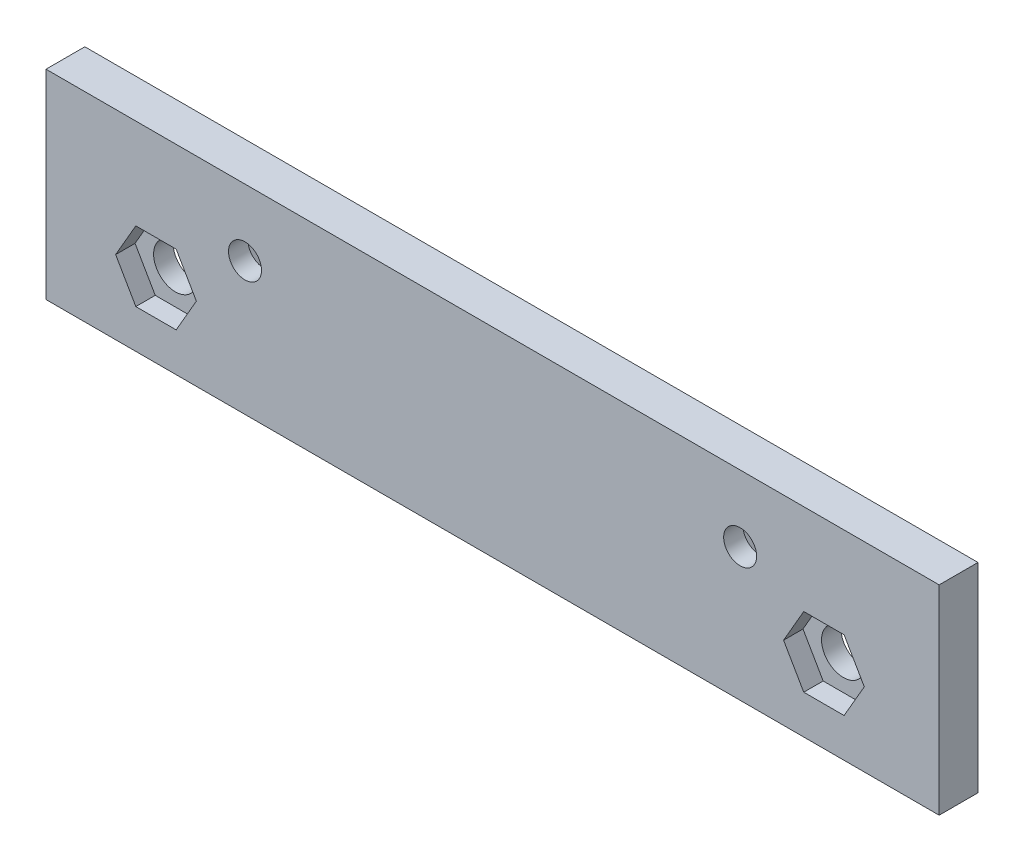
SolidWorks part; units mm, degrees
ref_plane "Front Plane" through (0, 0, 0) normal (0, 0, 1) x (1, 0, 0)
ref_plane "Top Plane" through (0, 0, 0) normal (0, 1, 0) x (1, 0, 0)
ref_plane "Right Plane" through (0, 0, 0) normal (1, 0, 0) x (0, 0, -1)
sketch "Sketch1" plane through (0, 0, 0) normal (0, 0, 1) x (1, 0, 0)
  line L1 (46, -37.5) -> (-46, -37.5)
  line L2 (46, -37.5) -> (46, 37.5)
  line L3 (46, 37.5) -> (-46, 37.5)
  line L4 (-46, -37.5) -> (-46, 37.5)
  line L5 (46, -37.5) -> (-46, 37.5) construction
  line L6 (46, 37.5) -> (-46, -37.5) construction
  point P0 (0, 0)
  dimension "D1" = 92
  dimension "D2" = 75
extrude "Boss-Extrude1" add sketch "Sketch1" along normal blind 4
sketch "Sketch2" plane through (0, 0, 4) normal (0, 0, 1) x (1, 0, 0)
  line L0 (-34.6699, -1.6) -> (34.1301, -1.6) construction
  line L1 (46, 37.5) -> (-46, 37.5) construction
  point P6 (0, 0)
  dimension "D1" = 39.1
  dimension "D2" = 34.1301
  dimension "D3" = 68.8
hole_wizard "M4 Clearance Hole1" positions "Sketch3" profile "Sketch4" hole size "M4" standard "DIN" end condition through all
sketch "Sketch3" plane through (0, 0, 4) normal (0, 0, 1) x (1, 0, 0)
  point P0 (-34.6699, -1.6)
  point P3 (34.1301, -1.6)
sketch "Sketch4" plane through (-34.6699, -1.6, 4) normal (1, 0, 0) x (0, -1, 0)
  line L0 (0, 0) -> (0, 4)
  line L1 (0, 4) -> (2.25, 4)
  line L2 (2.25, 4) -> (2.25, 0)
  line L5 (2.25, 0) -> (0, 0)
  line L11 (0, -6.35) -> (0, 107.95) construction
  dimension "Thru Hole Dia." = 4.5
  dimension "Thru Hole Depth" = 4
sketch "Sketch5" plane through (0, 0, 4) normal (0, 0, 1) x (1, 0, 0)
  line L0 (-25.5, 4.5) -> (25.5, 4.5)
  line L1 (-46, -37.5) -> (46, -37.5) construction
  dimension "D1" = 51
  dimension "D2" = 25.5
  dimension "D3" = 42
hole_wizard "M3 Clearance Hole1" positions "Sketch6" profile "Sketch7" hole size "M3" standard "DIN" end condition through all
sketch "Sketch6" plane through (0, 0, 4) normal (0, 0, 1) x (1, 0, 0)
  point P0 (-25.5, 4.5)
  point P3 (25.5, 4.5)
sketch "Sketch7" plane through (-25.5, 4.5, 4) normal (1, 0, 0) x (0, -1, 0)
  line L0 (0, 0) -> (0, 4)
  line L1 (0, 4) -> (1.7, 4)
  line L2 (1.7, 4) -> (1.7, 0)
  line L5 (1.7, 0) -> (0, 0)
  line L11 (0, -6.35) -> (0, 107.95) construction
  dimension "Thru Hole Dia." = 3.4
  dimension "Thru Hole Depth" = 4
sketch "Sketch8" plane through (0, 0, 4) normal (0, 0, 1) x (1, 0, 0)
  line L1 (-30.513, -1.6) -> (-32.5914, 2)
  line L2 (-32.5914, 2) -> (-36.7483, 2)
  line L3 (-36.7483, 2) -> (-38.8268, -1.6)
  line L4 (-38.8268, -1.6) -> (-36.7483, -5.2)
  line L5 (-36.7483, -5.2) -> (-32.5914, -5.2)
  line L6 (-32.5914, -5.2) -> (-30.513, -1.6)
  line L7 (29.9732, -1.6) -> (32.0517, -5.2)
  line L8 (32.0517, -5.2) -> (36.2086, -5.2)
  line L9 (36.2086, -5.2) -> (38.287, -1.6)
  line L10 (38.287, -1.6) -> (36.2086, 2)
  line L11 (36.2086, 2) -> (32.0517, 2)
  line L12 (32.0517, 2) -> (29.9732, -1.6)
  circle A0 centre (-34.6699, -1.6) radius 3.6 construction
  circle A1 centre (34.1301, -1.6) radius 3.6 construction
  dimension "D1" = 7.2
extrude "Cut-Extrude1" cut sketch "Sketch8" against normal blind 2
sketch "Sketch9" plane through (0, 0, 0) normal (0, 0, -1) x (-1, 0, 0)
  line L1 (-22.2091, 4.5) -> (-23.8546, 7.35)
  line L2 (-23.8546, 7.35) -> (-27.1454, 7.35)
  line L3 (-27.1454, 7.35) -> (-28.7909, 4.5)
  line L4 (-28.7909, 4.5) -> (-27.1454, 1.65)
  line L5 (-27.1454, 1.65) -> (-23.8546, 1.65)
  line L6 (-23.8546, 1.65) -> (-22.2091, 4.5)
  line L7 (22.2091, 4.5) -> (23.8546, 1.65)
  line L8 (23.8546, 1.65) -> (27.1454, 1.65)
  line L9 (27.1454, 1.65) -> (28.7909, 4.5)
  line L10 (28.7909, 4.5) -> (27.1454, 7.35)
  line L11 (27.1454, 7.35) -> (23.8546, 7.35)
  line L12 (23.8546, 7.35) -> (22.2091, 4.5)
  circle A0 centre (-25.5, 4.5) radius 2.85 construction
  circle A1 centre (25.5, 4.5) radius 2.85 construction
  dimension "D1" = 5.7
extrude "Cut-Extrude2" cut sketch "Sketch9" against normal blind 2
sketch "Sketch10" plane through (0, 0, 0) normal (0, 0, -1) x (-1, 0, 0)
  line L0 (46, 37.5) -> (46, -37.5) construction
  line L1 (-46, 37.5) -> (46, 37.5)
  line L2 (-46, 37.5) -> (-46, 11.35)
  line L3 (-46, 11.35) -> (46, 11.35)
  line L4 (46, 37.5) -> (46, 11.35)
  line L5 (-23.8546, 7.35) -> (-27.1454, 7.35) construction
  line L6 (-46, -37.5) -> (46, -37.5)
  line L7 (-46, -37.5) -> (-46, -9.2)
  line L8 (-46, -9.2) -> (46, -9.2)
  line L9 (46, -37.5) -> (46, -9.2)
  line L10 (-32.0517, -5.2) -> (-36.2086, -5.2) construction
  dimension "D1" = 4
  dimension "D2" = 4
extrude "Cut-Extrude3" cut sketch "Sketch10" against normal blind 4
